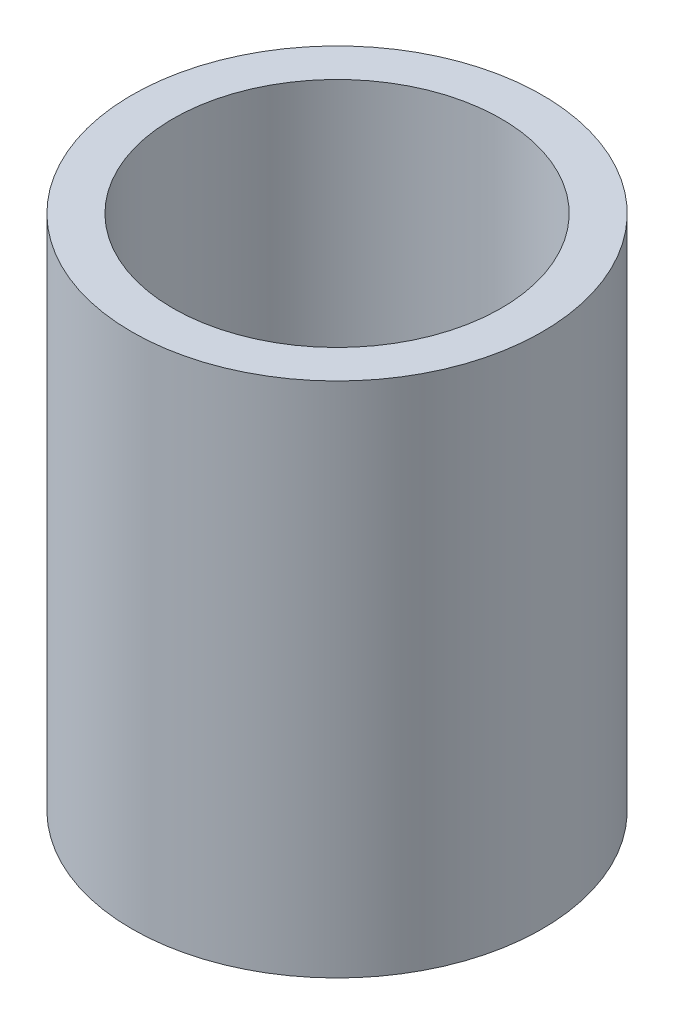
SolidWorks part; units mm, degrees
ref_plane "Front Plane" through (0, 0, 0) normal (0, 0, 1) x (1, 0, 0)
ref_plane "Top Plane" through (0, 0, 0) normal (0, 1, 0) x (1, 0, 0)
ref_plane "Right Plane" through (0, 0, 0) normal (1, 0, 0) x (0, 0, -1)
sketch "Sketch1" plane through (0, 0, 0) normal (0, 1, 0) x (1, 0, 0)
  circle A0 centre (0, 0) radius 6.35
  circle A1 centre (0, 0) radius 7.9375
  dimension "D1" = 12.7
  dimension "D2" = 15.875
extrude "Boss-Extrude1" add sketch "Sketch1" along normal blind 20
